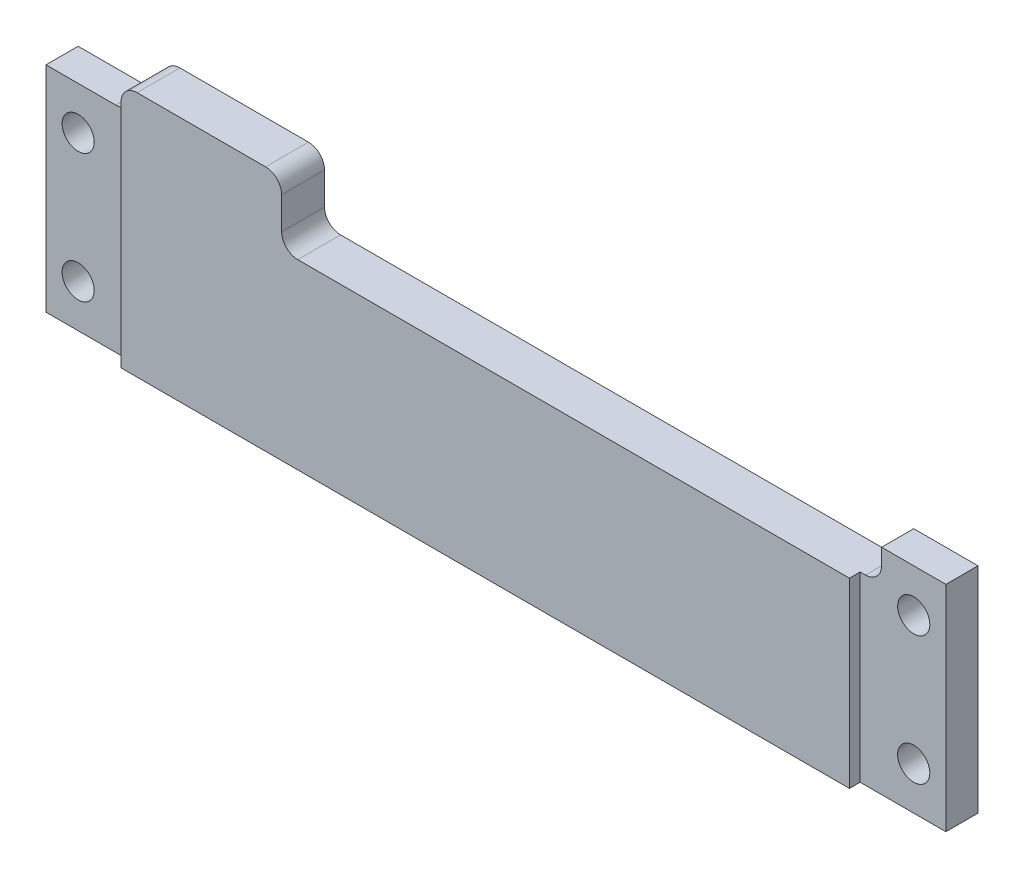
SolidWorks part; units mm, degrees
material "ABS PC"
ref_plane "Front Plane" through (0, 0, 0) normal (0, 0, 1) x (1, 0, 0)
ref_plane "Top Plane" through (0, 0, 0) normal (0, 1, 0) x (1, 0, 0)
ref_plane "Right Plane" through (0, 0, 0) normal (1, 0, 0) x (0, 0, -1)
sketch "Sketch1" plane through (0, 0, 0) normal (0, 0, 1) x (1, 0, 0)
  line L0 (23, 23) -> (23, 17)
  line L1 (23, 17) -> (78, 17)
  line L2 (0, 0) -> (84, 0)
  line L3 (78, 17) -> (78, 20)
  line L4 (78, 20) -> (84, 20)
  line L5 (84, 0) -> (84, 20)
  line L6 (23, 23) -> (8, 23)
  line L7 (8, 23) -> (8, 20)
  line L8 (8, 20) -> (0, 20)
  line L11 (0, 20) -> (0, 0)
  circle A0 centre (3, 16) radius 1.5
  circle A1 centre (81, 16) radius 1.5
  circle A2 centre (3, 4) radius 1.5
  circle A3 centre (81, 4) radius 1.5
  dimension "D5" = 3
  dimension "D1" = 4
  dimension "D2" = 4
  dimension "D3" = 84
  dimension "D4" = 20
  dimension "D6" = 3
  dimension "D7" = 3
  dimension "D8" = 3
  dimension "D9" = 6
  dimension "D10" = 55
  dimension "D11" = 8
  dimension "D12" = 3
extrude "Boss-Extrude1" add sketch "Sketch1" along normal blind 4
sketch "Sketch2" plane through (0, 0, 4) normal (0, 0, 1) x (1, 0, 0)
  line L0 (0, 0) -> (84, 0) construction
  line L1 (0, 20) -> (8, 20)
  line L2 (0, 20) -> (0, 0)
  line L3 (0, 0) -> (8, 0)
  line L4 (8, 20) -> (8, 0)
  line L6 (76, 0) -> (84, 0)
  line L7 (76, 0) -> (76, 20)
  line L8 (76, 20) -> (84, 20)
  line L9 (84, 0) -> (84, 20)
  dimension "D1" = 8
  dimension "D2" = 8
extrude "Cut-Extrude1" cut sketch "Sketch2" against normal blind 1
fillet "Fillet1" radius 1.5 5 edges at (78, 17, 1.5) (23, 17, 2) (23, 23, 2) (8, 23, 2) (8, 20, 1.5)
